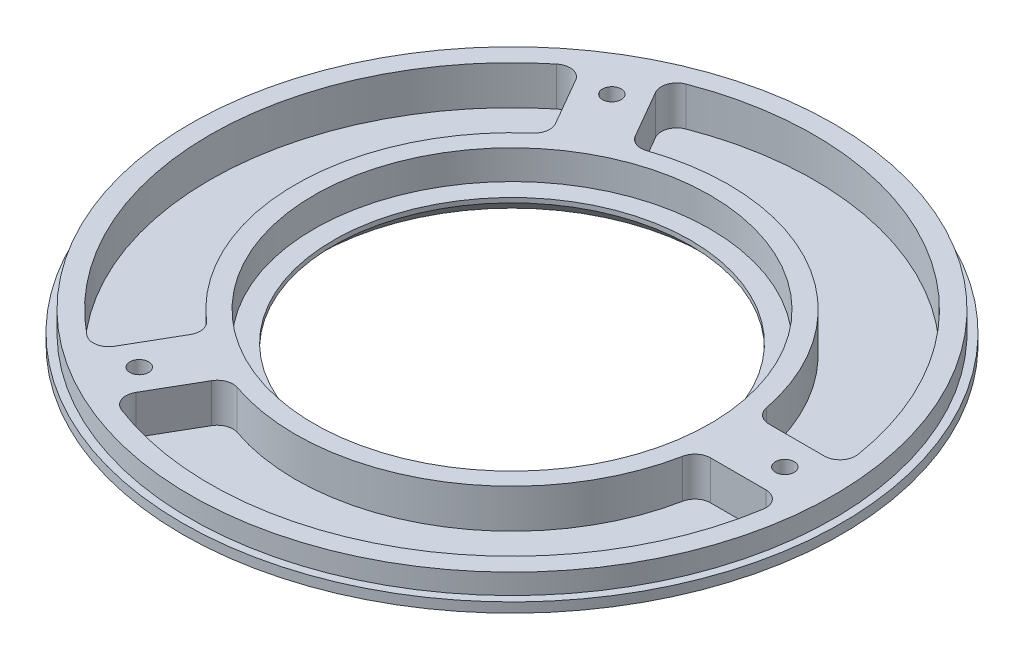
SolidWorks part; units mm, degrees
material "6061-T6 (SS)"
ref_plane "Front Plane" through (0, 0, 0) normal (0, 0, 1) x (1, 0, 0)
ref_plane "Top Plane" through (0, 0, 0) normal (0, 1, 0) x (1, 0, 0)
ref_plane "Right Plane" through (0, 0, 0) normal (1, 0, 0) x (0, 0, -1)
sketch "Sketch2" plane through (0, 0, 0) normal (1, 0, 0) x (0, 0, -1)
  line L0 (-45.8, 0) -> (-82.55, 0)
  line L1 (-82.55, 0) -> (-82.55, 12.7)
  line L2 (-82.55, 12.7) -> (-50.8, 12.7)
  line L3 (-45.8, 0) -> (-45.8, 5.2)
  line L4 (-45.8, 5.2) -> (-50.8, 5.2)
  line L5 (-50.8, 5.2) -> (-50.8, 12.7)
  line L6 (-80.2166, 12.7) -> (-80.2166, 0) construction
  dimension "D1" = 82.55
  dimension "D2" = 12.7
  dimension "D3" = 50.8
  dimension "D4" = 5
  dimension "D5" = 7.5
ref_axis "Axis1" through (0, -0.9004, 0) along (0, 1, 0)
revolve "Revolve1" add sketch "Sketch2" angle 360 about axis through (0, -0.9004, 0) along (0, 1, 0)
hole_wizard "#90 (0.0087) Diameter Hole1" positions "Sketch6" profile "Sketch7" hole size "#90" standard "ANSI Inch" end condition through all
sketch "Sketch6" plane through (0, 12.7, 0) normal (0, 1, 0) x (1, 0, 0)
  line L0 (0, 0) -> (-69.8201, 120.932) construction
  line L2 (0, 0) -> (0, 109.0908) construction
  point P0 (-35, 60.6218)
  dimension "D1" = 30
  dimension "D2" = 70
sketch "Sketch7" plane through (-35, 12.7, -60.6218) normal (1, 0, 0) x (0, 0, 1)
  line L0 (0, 0) -> (0, 12.7)
  line L1 (0, 12.7) -> (0.1105, 12.7)
  line L2 (0.1105, 12.7) -> (0.1105, 0)
  line L5 (0.1105, 0) -> (0, 0)
  line L11 (0, -6.35) -> (0, 107.95) construction
  dimension "Thru Hole Dia." = 0.221
  dimension "Thru Hole Depth" = 12.7
pattern_circular "CirPattern3" count 3 over 360 about axis through (0, -0.9004, 0) along (0, 1, 0) of "#90 (0.0087) Diameter Hole1"
sketch "Sketch8" plane through (0, 12.7, 0) normal (0, 1, 0) x (1, 0, 0)
  line L4 (0, 0) -> (46.9997, 81.4059) construction
  line L5 (-21.0255, 51.4172) -> (-32.098, 70.5955)
  line L6 (55.0414, 7.5) -> (77.1865, 7.5)
  line L7 (0, 0) -> (-35, 60.6218) construction
  arc A0 (-21.0255, 51.4172) -> (55.0414, 7.5) centre (0, 0) cw
  arc A1 (-32.098, 70.5955) -> (77.1865, 7.5) centre (0, 0) cw
  circle A2 centre (0, 0) radius 82.55 construction
  dimension "D1" = 27
  dimension "D2" = 5
  dimension "D3" = 7.5
  dimension "D4" = 60
extrude "Cut-Extrude1" cut sketch "Sketch8" against normal blind 10
fillet "Fillet1" radius 4 4 edges at (-21.0255, 7.7, -51.4172) (55.0414, 7.7, -7.5) (77.1865, 7.7, -7.5) (-32.098, 7.7, -70.5955)
pattern_circular "CirPattern4" count 3 over 360 about axis through (0, -0.9004, 0) along (0, 1, 0) of "Cut-Extrude1", "Fillet1"
chamfer "Chamfer1" distance 4 angle 45 1 edges at (0, 0, -45.8)
sketch "Sketch10" plane through (0, 0, 0) normal (0, -1, 0) x (1, 0, 0)
  circle A0 centre (0, 0) radius 82.55
  circle A1 centre (0, 0) radius 84.55
  circle A2 centre (0, 0) radius 82.55 construction
  dimension "D1" = 2
extrude "Boss-Extrude1" add sketch "Sketch10" against normal blind 7.5
chamfer "Chamfer3" distance 5 angle 60 1 edges at (0, 0, -84.55) first distance on face at (0, 7.5, -84.55)
fillet "Fillet4" radius 5 1 edges at (0, 0, 75.8897)
hole_wizard "#12 (0.189) Diameter Hole1" positions "Sketch13" profile "Sketch14" hole size "#12" standard "ANSI Inch" end condition through all
sketch "Sketch13" plane through (0, 0, 0) normal (0, -1, 0) x (-1, 0, 0)
  point P4 (35, 60.6218)
sketch "Sketch14" plane through (-35, 0, -60.6218) normal (1, 0, 0) x (0, 0, -1)
  line L0 (0, 0) -> (0, 12.7)
  line L1 (0, 12.7) -> (2.4003, 12.7)
  line L2 (2.4003, 12.7) -> (2.4003, 0)
  line L5 (2.4003, 0) -> (0, 0)
  line L11 (0, -6.35) -> (0, 107.95) construction
  dimension "Thru Hole Dia." = 4.8006
  dimension "Thru Hole Depth" = 12.7
pattern_circular "CirPattern5" count 3 over 360 about axis through (0, -0.9004, 0) along (0, 1, 0) of "#12 (0.189) Diameter Hole1"
equation "\"TubeDiameter\" = 6.500in"
